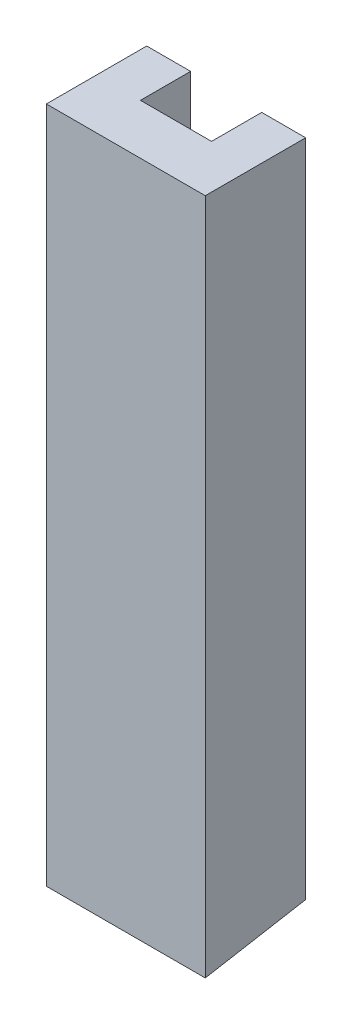
SolidWorks part; units mm, degrees
ref_plane "Front Plane" through (0, 0, 0) normal (0, 0, 1) x (1, 0, 0)
ref_plane "Top Plane" through (0, 0, 0) normal (0, 1, 0) x (1, 0, 0)
ref_plane "Right Plane" through (0, 0, 0) normal (1, 0, 0) x (0, 0, -1)
sketch "Sketch1" plane through (0, 0, 0) normal (0, 0, 1) x (1, 0, 0)
  line L1 (-9.7143, 13.1912) -> (9.2857, 13.1912)
  line L2 (-9.7143, 13.1912) -> (-9.7143, -67.8088)
  line L3 (-9.7143, -67.8088) -> (9.2857, -67.8088)
  line L4 (9.2857, 13.1912) -> (9.2857, -67.8088)
  dimension "D1" = 19
  dimension "D2" = 81
extrude "Boss-Extrude1" add sketch "Sketch1" along normal blind 12
sketch "Sketch2" plane through (0, 0, 0) normal (0, 0, -1) x (-1, 0, 0)
  line L0 (0.2143, 16.8694) -> (0.2143, -71.6226) construction
  line L5 (-9.2857, -67.8088) -> (-9.2857, 13.1912) construction
  line L6 (9.7143, 13.1912) -> (9.7143, -67.8088) construction
  line L7 (-9.2857, 13.1912) -> (9.7143, 13.1912) construction
  line L8 (-4.0357, 13.1912) -> (4.4643, 13.1912)
  line L9 (-4.0357, 13.1912) -> (-4.0357, -67.8088)
  line L10 (-4.0357, -67.8088) -> (4.4643, -67.8088)
  line L11 (4.4643, 13.1912) -> (4.4643, -67.8088)
  line L13 (9.7143, -67.8088) -> (-9.2857, -67.8088) construction
  dimension "D1" = 8.5
extrude "Cut-Extrude1" cut sketch "Sketch2" against normal blind 6
ref_plane "Plane1" through (0, -63.712, -11.2341) normal (0, -0.9848, -0.1736) x (1, 0, 0)
sketch "Sketch3" plane through (0, -63.712, -11.2341) normal (0, -0.9848, -0.1736) x (1, 0, 0)
  line L9 (-16.6295, 27.5301) -> (15.1549, 27.5301)
  line L10 (-16.6295, 27.5301) -> (-16.6295, 7.4455)
  line L11 (-16.6295, 7.4455) -> (15.1549, 7.4455)
  line L12 (15.1549, 27.5301) -> (15.1549, 7.4455)
extrude "Cut-Extrude2" cut sketch "Sketch3" along normal through all
